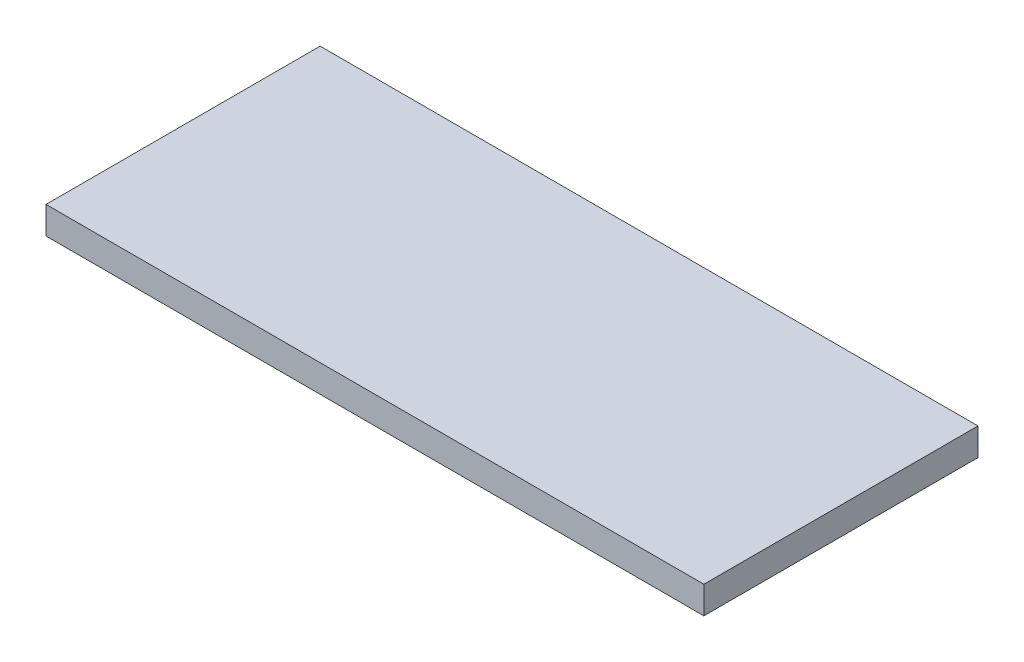
SolidWorks part; units mm, degrees
ref_plane "Front Plane" through (0, 0, 0) normal (0, 0, 1) x (1, 0, 0)
ref_plane "Top Plane" through (0, 0, 0) normal (0, 1, 0) x (1, 0, 0)
ref_plane "Right Plane" through (0, 0, 0) normal (1, 0, 0) x (0, 0, -1)
sketch "Sketch1" plane through (0, 0, 0) normal (0, 1, 0) x (1, 0, 0)
  line L1 (-55.9961, 103.4765) -> (248.8039, 103.4765)
  line L2 (-55.9961, 103.4765) -> (-55.9961, -23.5235)
  line L3 (-55.9961, -23.5235) -> (248.8039, -23.5235)
  line L4 (248.8039, 103.4765) -> (248.8039, -23.5235)
  dimension "D1" = 127
  dimension "D2" = 304.8
extrude "Boss-Extrude1" add sketch "Sketch1" along normal blind 12.7
